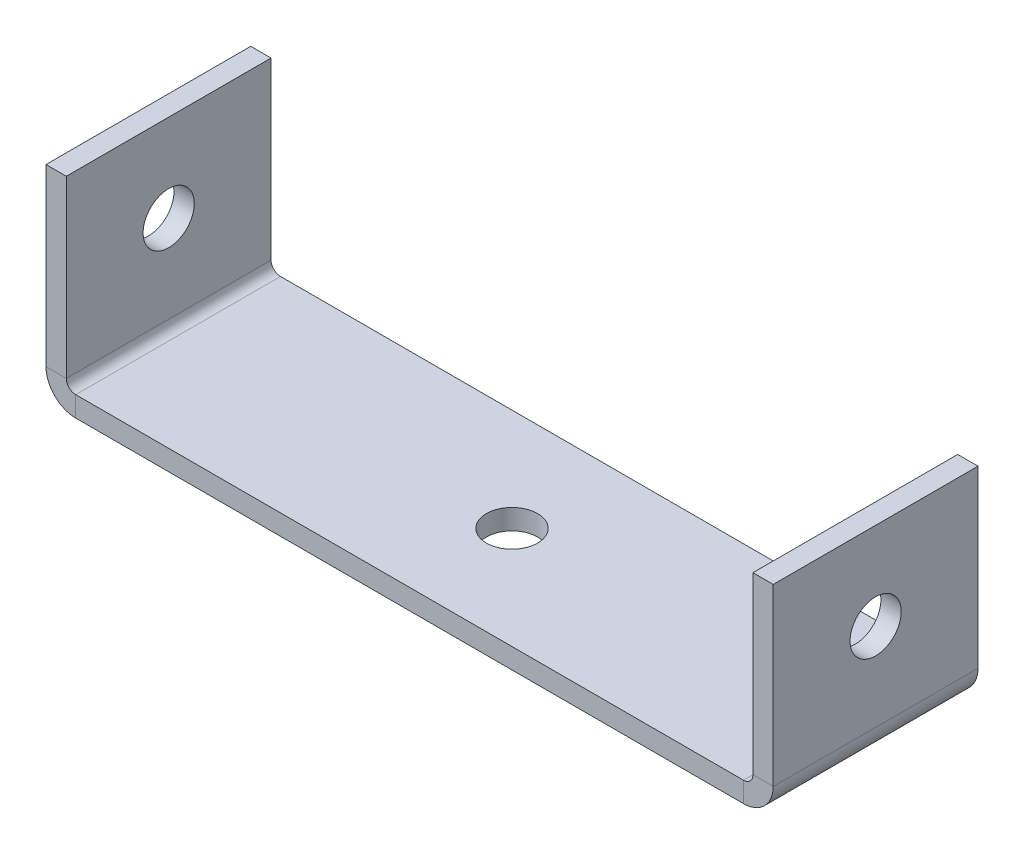
SolidWorks part; units mm, degrees
note: The reader was unsure of these and kept them because the rebuilt part matched: flange length of "Edge-Flange1".
ref_plane "Front Plane" through (0, 0, 0) normal (0, 0, 1) x (1, 0, 0)
ref_plane "Top Plane" through (0, 0, 0) normal (0, 1, 0) x (1, 0, 0)
ref_plane "Right Plane" through (0, 0, 0) normal (1, 0, 0) x (0, 0, -1)
sketch "Sketch1" plane through (0, 0, 0) normal (0, 1, 0) x (1, 0, 0)
  line L1 (0, 0) -> (56.83, 0)
  line L2 (0, 0) -> (0, 16)
  line L3 (0, 16) -> (56.83, 16)
  line L4 (56.83, 0) -> (56.83, 16)
  circle A0 centre (28.415, 8) radius 2
  point P0 (0, 0)
  point P8 (0, 8)
  point P9 (28.415, 16)
  dimension "D4" = 4
  dimension "D1" = 56.83
  dimension "D2" = 16
base flange "Base-Flange1" sketch "Sketch1" thickness 1.5875 reverse thickness direction no parameters "D1"=0.7366
edge flange "Edge-Flange1" sketch "Sketch10" flange profiles "Sketch10", "Sketch11" flange angle 90 flange length 16 flange position material inside bend radius 0.7366 thickness 1.5875 relief rectangular parameters "D6"=10, "D8"=1
sketch "Sketch10" plane through (56.83, 0, 0) normal (1, 0, 0) x (0, 0, -1)
  line L2 (0, 0) -> (0, 14.4125)
  line L3 (0, 14.4125) -> (16, 14.4125)
  line L4 (16, 14.4125) -> (16, 0)
  line L7 (0, 0) -> (16, 0) construction
  line L8 (0, 0) -> (16, 0)
sketch "Sketch11" plane through (0, 0, 0) normal (-1, 0, 0) x (0, 0, 1)
  line L0 (-16, 0) -> (0, 0) construction
  line L1 (-16, 0) -> (0, 0)
  line L2 (-16, 0) -> (-16, 14.4125)
  line L3 (-16, 14.4125) -> (0, 14.4125)
  line L4 (0, 14.4125) -> (0, 0)
bend "EdgeBend1" bend radius 0.7366 bend angle 90 parameters "D5"=1
bend "EdgeBend2" bend radius 0.7366 bend angle 90 parameters "D5"=2
sketch "Sketch12" plane through (56.83, 0, 0) normal (1, 0, 0) x (0, 0, -1)
  line L0 (16, 14.4125) -> (0, 14.4125) construction
  line L1 (16, 0.7366) -> (16, 14.4125) construction
  circle A0 centre (8, 7.5746) radius 2
  point P4 (8, 14.4125)
  point P7 (16, 7.5746)
  dimension "D1" = 4
extrude "Cut-Extrude1" cut sketch "Sketch12" against normal through all normal cut yes
sketch "Bend-Lines1" [suppressed] plane through (0, 0, 0) normal (0, 1, 0) x (1, 0, 0)
sketch "Bounding-Box1" [suppressed] plane through (0, 0, 0) normal (0, 1, 0) x (1, 0, 0)
sheet metal parameters "Sheet-Metal1" thickness 1.5875 parameters "D1"=0.7366
flat pattern "Flat-Pattern1" [suppressed]
sketch "Bend-Lines2" plane through (0, 0, 0) normal (0, 1, 0) x (1, 0, 0)
sketch3d "Bounding-Box2" [suppressed]
  line L0 (-56.83, 16, 0) -> (0, 16, 0) construction
  line L1 (-56.83, 0, 0) -> (0, 0, 0) construction
  line L2 (-56.83, 16, 0) -> (-56.83, 0, 0) construction
  line L3 (0, 16, 0) -> (0, 0, 0) construction
sheet metal parameters "Sheet-Metal2" thickness 1.5875 parameters "D1"=0.7366
flat pattern "Flat-Pattern1"
sketch "Bend-Lines2" plane through (0, 0, 0) normal (0, 1, 0) x (1, 0, 0)
  line L0 (1.1222, 16) -> (1.1222, 0) construction
  line L1 (55.7078, 0) -> (55.7078, 16) construction
  line L2 (1.1222, 16) -> (1.1222, 0) construction
  line L3 (55.7078, 0) -> (55.7078, 16) construction
sketch3d "Bounding-Box2" [suppressed]
  line L0 (70.5857, 16, 0) -> (-13.7557, 16, 0) construction
  line L1 (70.5857, 0, 0) -> (-13.7557, 0, 0) construction
  line L2 (70.5857, 16, 0) -> (70.5857, 0, 0) construction
  line L3 (-13.7557, 16, 0) -> (-13.7557, 0, 0) construction
bend of the flat pattern "Flatten-<EdgeBend1>1"
bend of the flat pattern "Flatten-<EdgeBend2>1"
sheet metal parameters "Sheet-Metal3" thickness 1.5875 parameters "D1"=0.7366
flat pattern "Flat-Pattern1"
sketch "Bend-Lines2" plane through (0, 0, 0) normal (0, 1, 0) x (1, 0, 0)
  line L0 (1.1222, 16) -> (1.1222, 0) construction
  line L1 (55.7078, 0) -> (55.7078, 16) construction
  line L2 (1.1222, 16) -> (1.1222, 0) construction
  line L3 (55.7078, 0) -> (55.7078, 16) construction
sketch3d "Bounding-Box2" [suppressed]
  line L0 (70.5857, 16, 0) -> (-13.7557, 16, 0) construction
  line L1 (70.5857, 0, 0) -> (-13.7557, 0, 0) construction
  line L2 (70.5857, 16, 0) -> (70.5857, 0, 0) construction
  line L3 (-13.7557, 16, 0) -> (-13.7557, 0, 0) construction
bend of the flat pattern "Flatten-<EdgeBend1>1"
bend of the flat pattern "Flatten-<EdgeBend2>1"
